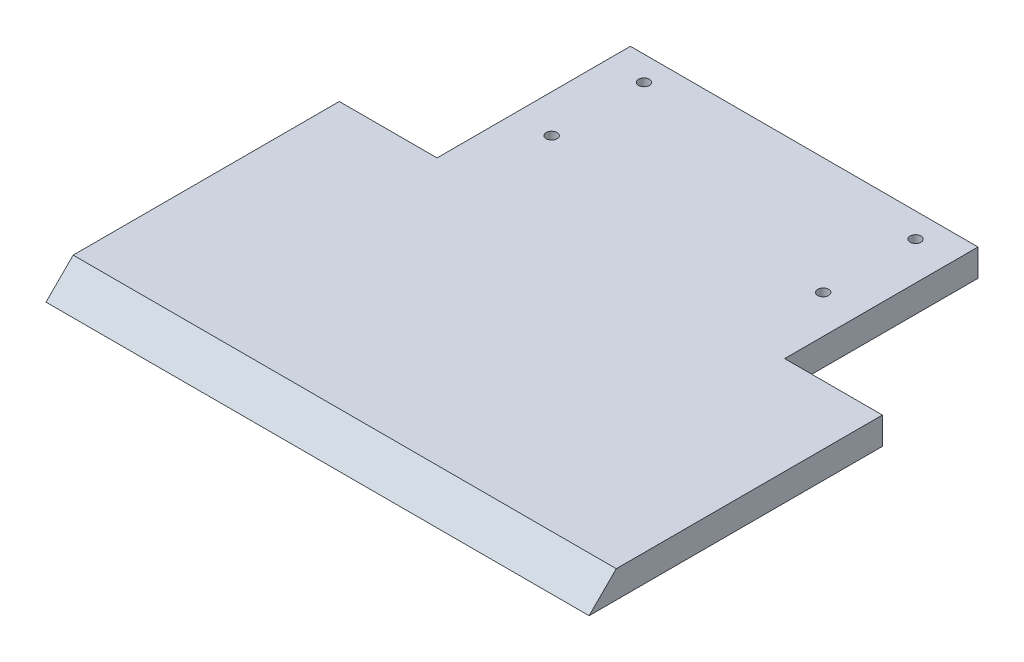
SolidWorks part; units mm, degrees
ref_plane "Alzado" through (0, 0, 0) normal (0, 0, 1) x (1, 0, 0)
ref_plane "Planta" through (0, 0, 0) normal (0, 1, 0) x (1, 0, 0)
ref_plane "Vista lateral" through (0, 0, 0) normal (1, 0, 0) x (0, 0, -1)
sketch "Croquis2" plane through (0, 0, 0) normal (0, 1, 0) x (1, 0, 0)
  line L1 (0, 0) -> (100, 0)
  line L2 (0, 0) -> (0, 99.2)
  line L3 (0, 99.2) -> (100, 99.2)
  line L4 (100, 0) -> (100, 99.2)
  dimension "D1" = 100
  dimension "D2" = 99.2
extrude "Saliente-Extruir1" add sketch "Croquis2" along normal blind 5
chamfer "Chaflán1" distance 5 angle 45 1 edges at (50, 5, 0)
sketch "Croquis3" plane through (0, 5, 0) normal (0, 1, 0) x (1, 0, 0)
  line L1 (0, 99.2) -> (18, 99.2)
  line L2 (0, 99.2) -> (0, 54)
  line L3 (0, 54) -> (18, 54)
  line L4 (18, 99.2) -> (18, 54)
  line L5 (100, 99.2) -> (82, 99.2)
  line L6 (100, 99.2) -> (100, 54)
  line L7 (100, 54) -> (82, 54)
  line L8 (82, 99.2) -> (82, 54)
  dimension "D1" = 45.2
  dimension "D2" = 18
  dimension "D3" = 45.2
  dimension "D4" = 18
extrude "Cortar-Extruir1" cut sketch "Croquis3" against normal blind 5
sketch "Croquis6" plane through (0, 5, 0) normal (0, 1, 0) x (1, 0, 0)
  line L0 (18, 76.6) -> (39.8747, 76.6) construction
  line L1 (18, 54) -> (18, 99.2) construction
  line L2 (82, 76.6) -> (66.6645, 76.6) construction
  line L3 (82, 99.2) -> (82, 54) construction
  circle A0 centre (25, 85.1) radius 1
  circle A1 centre (25, 68.1) radius 1
  circle A2 centre (75, 85.1) radius 1
  circle A3 centre (75, 68.1) radius 1
  dimension "D1" = 2
  dimension "D2" = 2
  dimension "D3" = 2
  dimension "D4" = 2
  dimension "D5" = 17
  dimension "D6" = 17
  dimension "D7" = 7
  dimension "D8" = 7
  dimension "D9" = 7
  dimension "D10" = 7
  dimension "D11" = 8.5
  dimension "D12" = 8.5
extrude "Cortar-Extruir3" cut sketch "Croquis6" against normal blind 10
sketch "Croquis8" plane through (0, 5, 0) normal (0, 1, 0) x (1, 0, 0)
  line L0 (18, 89.6) -> (82, 89.6) construction
  line L1 (18, 54) -> (18, 99.2) construction
  line L2 (82, 99.2) -> (82, 54) construction
  line L4 (18, 99.2) -> (82, 99.2)
  line L5 (18, 99.2) -> (18, 89.6)
  line L6 (18, 89.6) -> (82, 89.6)
  line L7 (82, 99.2) -> (82, 89.6)
  circle A0 centre (25, 85.1) radius 1 construction
  dimension "D1" = 4.5
extrude "Cortar-Extruir4" cut sketch "Croquis8" against normal through all
